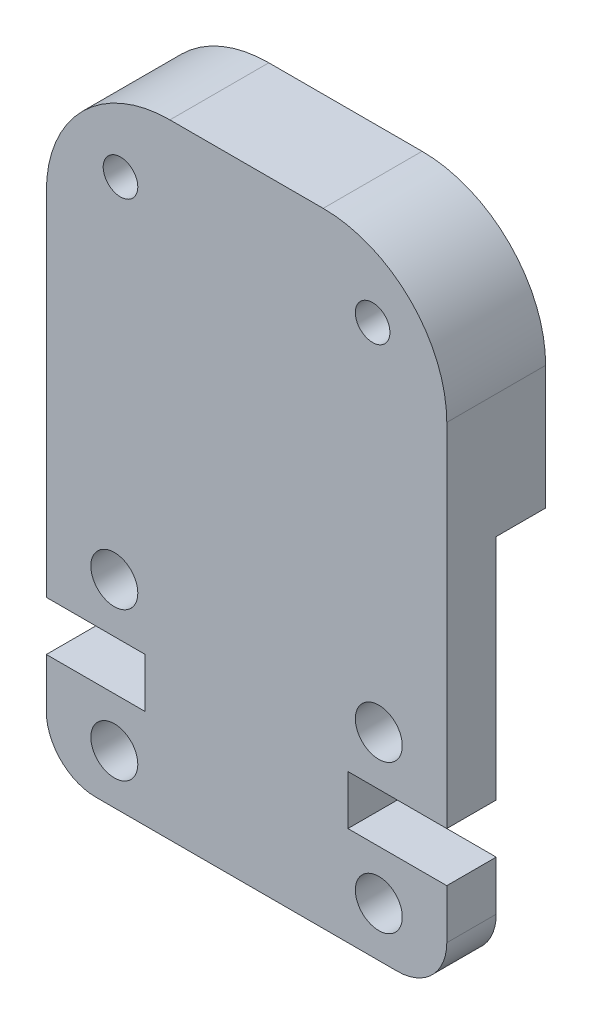
SolidWorks part; units mm, degrees
ref_plane "Front Plane" through (0, 0, 0) normal (0, 0, 1) x (1, 0, 0)
ref_plane "Top Plane" through (0, 0, 0) normal (0, 1, 0) x (1, 0, 0)
ref_plane "Right Plane" through (0, 0, 0) normal (1, 0, 0) x (0, 0, -1)
sketch "Sketch1" plane through (0, 0, 0) normal (0, 0, 1) x (1, 0, 0)
  line L0 (8.1, 25.23) -> (8.1, 0) construction
  line L1 (2, 0) -> (14.2, 0)
  line L2 (5, 25.23) -> (11.2, 25.23)
  line L3 (12.2, 4) -> (16.2, 4)
  line L4 (12.2, 6) -> (12.2, 4)
  line L5 (16.2, 6) -> (12.2, 6)
  line L6 (16.2, 2) -> (16.2, 4)
  line L7 (16.2, 20.23) -> (16.2, 6)
  line L22 (0, 20.23) -> (0, 6)
  line L33 (0, 2) -> (0, 4)
  line L34 (0, 6) -> (4, 6)
  line L36 (4, 6) -> (4, 4)
  line L37 (4, 4) -> (0, 4)
  circle A0 centre (13.45, 2) radius 0.95
  arc A1 (16.2, 2) -> (14.2, 0) centre (14.2, 2) cw
  circle A2 centre (13.2, 22.23) radius 0.7
  arc A3 (11.2, 25.23) -> (16.2, 20.23) centre (11.2, 20.23) cw
  circle A4 centre (2.75, 8) radius 0.95
  circle A5 centre (13.45, 8) radius 0.95
  arc A17 (5, 25.23) -> (0, 20.23) centre (5, 20.23) ccw
  circle A19 centre (3, 22.23) radius 0.7
  arc A21 (0, 2) -> (2, 0) centre (2, 2) ccw
  circle A23 centre (2.75, 2) radius 0.95
  dimension "D1" = 1.4
  dimension "D3" = 5
  dimension "D4" = 2
  dimension "D10" = 1.9
  dimension "D11" = 1.9
  dimension "D14" = 1.9
  dimension "D15" = 1.9
  dimension "D5" = 3
  dimension "D7" = 8.1
  dimension "D13" = 25.23
  dimension "D12" = 3
  dimension "D2" = 6
  dimension "D6" = 2.75
  dimension "D8" = 2.75
  dimension "D9" = 4
extrude "Boss-Extrude1" add sketch "Sketch1" along normal blind 4
sketch "Sketch2" plane through (0, 0, 0) normal (0, 0, 1) x (1, 0, 0)
  line L0 (0, 0) -> (16.2, 0)
  line L1 (16.2, 0) -> (16.2, 15.23)
  line L2 (16.2, 15.23) -> (0, 15.23)
  line L3 (0, 15.23) -> (0, 0)
  dimension "D1" = 15.23
extrude "Cut-Extrude1" cut sketch "Sketch2" along normal blind 2
equation "\"D7@Sketch1\"= \"fingerWidth@parametersSketch@prostheticParameters.SLDPRT\" / 2 'DIP width"
equation "\"D13@Sketch1\"= \"HL@parametersSketch@prostheticParameters.SLDPRT\" * 0.158 - 4 'DIP length - Sil. Sht DIP"
equation "\"D1@Sketch2\"= \"HL@parametersSketch@prostheticParameters.SLDPRT\" * 0.158 - 4 - 10 'DIP Cut fingertip"
equation "\"D1@Sketch1\"= 1 + \"tol1@parametersSketch@prostheticParameters.SLDPRT\""
equation "\"D10@Sketch1\"= 1.5 + \"tol1@parametersSketch@prostheticParameters.SLDPRT\""
equation "\"D11@Sketch1\"= 1.5 + \"tol1@parametersSketch@prostheticParameters.SLDPRT\""
equation "\"D14@Sketch1\"= 1.5 + \"tol1@parametersSketch@prostheticParameters.SLDPRT\""
equation "\"D15@Sketch1\"= 1.5 + \"tol1@parametersSketch@prostheticParameters.SLDPRT\""
